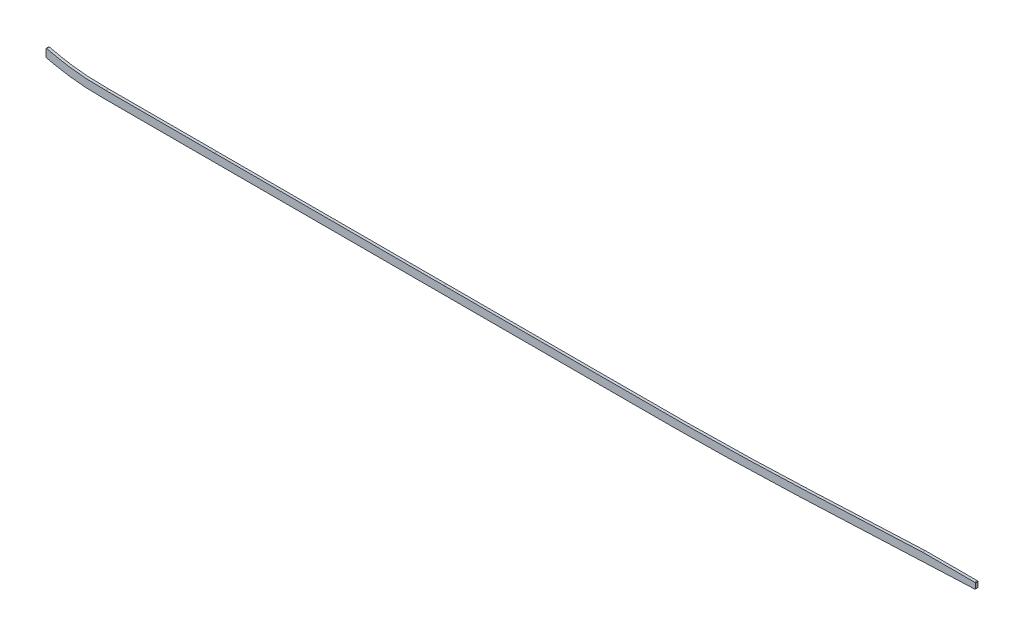
SolidWorks part; units mm, degrees
ref_plane "Front Plane" through (0, 0, 0) normal (0, 0, 1) x (1, 0, 0)
ref_plane "Top Plane" through (0, 0, 0) normal (0, 1, 0) x (1, 0, 0)
ref_plane "Right Plane" through (0, 0, 0) normal (1, 0, 0) x (0, 0, -1)
sketch "Sketch1" plane through (0, 0, 0) normal (0, 0, 1) x (1, 0, 0)
  line L0 (1046.2855, 53.4707) -> (499.61, 53.4707) construction
  line L1 (55, 0) -> (-55, 0) construction
  line L2 (1046.2855, -53.4707) -> (499.61, -53.4707)
  line L3 (1046.2855, -34.4207) -> (499.61, -34.4207)
  line L4 (99.06, -18.1493) -> (99.06, -37.7415)
  line L5 (2669.54, 9.5231) -> (2669.54, -9.569)
  spline S0 degree 5 poles (2699.7923, 7.5245) (2639.6368, 11.6572) (2579.4813, 15.4358) (2518.4981, 19.1485) (2436.3555, 23.2524) (2354.213, 26.6315) (2332.5703, 27.481) (2156.2686, 34.3778) (1979.9669, 41.6286) (1824.1143, 52.7713) (1636.9286, 53.5796) (1449.7429, 53.454) (1418.0067, 53.4707) (1324.8993, 53.4707) (1231.7919, 53.4707) (1170.4413, 53.4707) (1108.7841, 53.4707) (1047.1269, 53.4707) (1046.8464, 53.4707) (1046.5659, 53.4707) (1046.2855, 53.4707) knots 100.654805 100.654805 100.654805 100.654805 100.654805 100.654805 130.927897 130.927897 130.927897 141.337055 141.337055 141.337055 218.101815 218.101815 218.101815 233.772059 233.772059 233.772059 264.077723 264.077723 264.077723 264.216209 264.216209 264.216209 264.216209 264.216209 264.216209 weights 1 1 1 1 1 1 1 1 1 1 1 1 1 1 1 1 1 1 1 1 1 construction
  spline S1 degree 5 poles (499.61, 53.4707) (492.1368, 53.4707) (484.7543, 53.4707) (477.443, 53.4707) (448.5166, 53.4707) (419.5901, 53.4707) (398.3681, 53.4707) (355.6475, 53.4707) (312.927, 53.4707) (289.2351, 53.4703) (265.365, 53.4707) (241.4948, 53.4707) (241.4716, 53.4707) (241.4484, 53.4707) (241.4251, 53.4707) knots 19.90683 19.90683 19.90683 19.90683 19.90683 19.90683 23.637897 23.637897 23.637897 34.276546 34.276546 34.276546 46.401341 46.401341 46.401341 46.413154 46.413154 46.413154 46.413154 46.413154 46.413154 weights 1 1 1 1 1 1 1 1 1 1 1 1 1 1 1 construction
  spline S2 degree 5 poles (241.4251, 53.4707) (224.2869, 53.4707) (207.1495, 53.4673) (190.2039, 52.6866) (151.6561, 49.0319) (113.1083, 41.5037) (91.9499, 36.3426) (71.313, 30.9696) (50.6762, 24.7565) knots 0 0 0 0 0 0 8.713816 8.713816 8.713816 19.90683 19.90683 19.90683 19.90683 19.90683 19.90683 weights 1 1 1 1 1 1 1 1 1 construction
  spline S3 degree 5 poles (241.4251, -53.4707) (224.2869, -53.4707) (207.1495, -53.4673) (190.2039, -52.6866) (151.6561, -49.0319) (113.1083, -41.5037) (91.9499, -36.3426) (71.313, -30.9696) (50.6762, -24.7565) knots 0 0 0 0 0 0 8.713816 8.713816 8.713816 19.90683 19.90683 19.90683 19.90683 19.90683 19.90683 weights 1 1 1 1 1 1 1 1 1
  spline S4 degree 5 poles (499.61, -53.4707) (492.1368, -53.4707) (484.7543, -53.4707) (477.443, -53.4707) (448.5166, -53.4707) (419.5901, -53.4707) (398.3681, -53.4707) (355.6475, -53.4707) (312.927, -53.4707) (289.2351, -53.4703) (265.365, -53.4707) (241.4948, -53.4707) (241.4716, -53.4707) (241.4484, -53.4707) (241.4251, -53.4707) knots 19.90683 19.90683 19.90683 19.90683 19.90683 19.90683 23.637897 23.637897 23.637897 34.276546 34.276546 34.276546 46.401341 46.401341 46.401341 46.413154 46.413154 46.413154 46.413154 46.413154 46.413154 weights 1 1 1 1 1 1 1 1 1 1 1 1 1 1 1
  spline S5 degree 5 poles (2699.7923, -7.5245) (2639.6368, -11.6572) (2579.4813, -15.4358) (2518.4981, -19.1485) (2436.3555, -23.2524) (2354.213, -26.6315) (2332.5703, -27.481) (2156.2686, -34.3778) (1979.9669, -41.6286) (1824.1143, -52.7713) (1636.9286, -53.5796) (1449.7429, -53.454) (1418.0067, -53.4707) (1324.8993, -53.4707) (1231.7919, -53.4707) (1170.4413, -53.4707) (1108.7841, -53.4707) (1047.1269, -53.4707) (1046.8464, -53.4707) (1046.5659, -53.4707) (1046.2855, -53.4707) knots 100.654805 100.654805 100.654805 100.654805 100.654805 100.654805 130.927897 130.927897 130.927897 141.337055 141.337055 141.337055 218.101815 218.101815 218.101815 233.772059 233.772059 233.772059 264.077723 264.077723 264.077723 264.216209 264.216209 264.216209 264.216209 264.216209 264.216209 weights 1 1 1 1 1 1 1 1 1 1 1 1 1 1 1 1 1 1 1 1 1
  spline S6 degree 1 poles (2698.4867, 11.4807) (1046.2855, -34.4207) knots 0 0 1 1 construction
  spline S7 degree 1 poles (499.61, -34.4207) (241.4252, -34.4207) knots 0 0 1 1 construction
  spline S8 degree 1 poles (241.4252, -34.4207) (56.168, -6.5153) knots 0 0 1 1 construction
  spline S9 degree 3 poles (2698.4867, 11.4807) (2691.2474, 10.9833) (2679.1952, 10.1655) (2662.2765, 9.0388) (2635.6663, 7.2925) (2596.8577, 4.8261) (2545.7297, 1.7583) (2494.4053, -1.0986) (2451.533, -3.2666) (2417.1983, -4.8671) (2391.4571, -6.0036) (2365.6347, -7.0869) (2339.5463, -8.1377) (2313.4661, -9.1651) (2287.6124, -10.1795) (2261.7633, -11.201) (2227.2853, -12.5838) (2184.1756, -14.3661) (2132.4291, -16.6074) (2063.4255, -19.7089) (1977.1749, -23.7005) (1873.7325, -28.1494) (1770.3746, -31.6575) (1667.0857, -33.7931) (1581.0111, -34.3832) (1512.074, -34.4278) (1443.0615, -34.4095) (1356.8009, -34.4244) (1218.7946, -34.4185) (1115.289, -34.4207) (1046.2855, -34.4207) knots 100.654805 100.654805 100.654805 100.654805 102.842388 104.300777 105.766098 110.877392 115.988686 121.09998 126.211274 128.766921 131.322568 133.878215 136.433862 138.989509 141.545156 144.100803 146.656449 151.767743 156.879037 161.990331 172.212919 182.435507 192.658094 202.880682 213.10327 218.214564 223.325858 233.548445 243.771033 264.216209 264.216209 264.216209 264.216209
  spline S10 degree 3 poles (499.61, -34.4207) (488.6147, -34.4207) (472.2364, -34.4207) (449.9402, -34.4207) (427.7713, -34.4207) (405.8747, -34.4207) (384.5849, -34.4207) (368.9002, -34.4207) (353.3766, -34.4207) (332.6085, -34.4207) (306.2878, -34.4206) (274.0235, -34.4205) (252.271, -34.4207) (241.4252, -34.4207) knots 19.90683 19.90683 19.90683 19.90683 23.22012 24.876765 26.533411 29.846701 31.503346 33.159992 34.816637 36.473282 39.786573 43.099863 46.413154 46.413154 46.413154 46.413154
  spline S11 degree 3 poles (241.4252, -34.4207) (239.3949, -34.4207) (235.3223, -34.4205) (227.2744, -34.3987) (217.3194, -34.2975) (205.5307, -33.9764) (189.9633, -33.2126) (170.697, -31.5435) (147.5333, -28.3144) (125.4828, -24.2021) (107.4399, -20.1965) (92.2061, -16.4882) (75.9505, -12.2555) (63.6202, -8.7589) (56.168, -6.5153) knots 0 0 0 0 0.622088 1.244177 2.488354 3.732531 4.976707 7.465061 9.953415 12.441768 14.558235 15.802412 17.418476 19.90683 19.90683 19.90683 19.90683
  point P2 (0, 0)
  dimension "D1" = 50.6762
  dimension "D3" = 99.06
  dimension "D4" = 2669.54
  dimension "D2" = 19.05
extrude "Boss-Extrude1" add sketch "Sketch1" along normal mid plane 6.35 contours S10 S11 L4 S3 S4 L2 S5 L5 S9 L3 region at (1384.0143, -36.0059, 0)
sketch "Sketch2" plane through (0, 0, 3.175) normal (0, 0, 1) x (1, 0, 0)
  line L0 (2185.533, -14.3257) -> (2311.4, -14.3257)
  line L1 (2311.4, -14.3257) -> (2311.4, -9.2457)
  line L2 (2311.4, -14.3257) -> (2311.4, -28.3104)
  line L3 (2669.54, 9.5231) -> (2669.54, -9.569) construction
  line L4 (2669.54, 9.5231) -> (2669.54, -9.569)
  spline S0 degree 3 poles (689.0175, 232.3189) (4033.8285, 148.9311) (3356.6623, 54.6077) (2635.6663, 7.2925) (2596.8577, 4.8261) (2545.7297, 1.7583) (2494.4053, -1.0986) (2451.533, -3.2666) (2417.1983, -4.8671) (2391.4571, -6.0036) (2365.6347, -7.0869) (2339.5463, -8.1377) (2313.4661, -9.1651) (2287.6124, -10.1795) (2261.7633, -11.201) (2227.2853, -12.5838) (2184.1756, -14.3661) (2132.4291, -16.6074) (2063.4255, -19.7089) (1977.1749, -23.7005) (1873.7325, -28.1494) (1770.3746, -31.6575) (1667.0857, -33.7931) (1581.0111, -34.3832) (1512.074, -34.4278) (1443.0615, -34.4095) (1356.8009, -34.4244) (551.9641, -34.3896) (-218.4198, -34.7282) (-953.6342, -29.9632) knots -106.828462 -106.828462 -106.828462 -106.828462 104.300777 105.766098 110.877392 115.988686 121.09998 126.211274 128.766921 131.322568 133.878215 136.433862 138.989509 141.545156 144.100803 146.656449 151.767743 156.879037 161.990331 172.212919 182.435507 192.658094 202.880682 213.10327 218.214564 223.325858 233.548445 243.771033 461.793666 461.793666 461.793666 461.793666 only from (2669.54, 9.5231) to (1046.2855, -34.4207) construction
  spline S1 degree 3 poles (2669.54, 9.5231) (2667.1265, 9.3624) (2659.8616, 8.8803) (2635.6663, 7.2925) (2596.8577, 4.8261) (2545.7297, 1.7583) (2494.4053, -1.0986) (2451.533, -3.2666) (2417.1983, -4.8671) (2391.4571, -6.0036) (2365.6347, -7.0869) (2339.5463, -8.1377) (2313.4661, -9.1651) (2287.6124, -10.1795) (2261.7633, -11.201) (2227.2853, -12.5838) (2184.1756, -14.3661) (2132.4291, -16.6074) (2063.4255, -19.7089) (1977.1749, -23.7005) (1873.7325, -28.1494) (1770.3746, -31.6575) (1667.0857, -33.7931) (1581.0111, -34.3832) (1512.074, -34.4278) (1443.0615, -34.4095) (1356.8009, -34.4244) (1218.7946, -34.4185) (1115.289, -34.4207) (1046.2855, -34.4207) knots 103.571583 103.571583 103.571583 103.571583 104.300777 105.766098 110.877392 115.988686 121.09998 126.211274 128.766921 131.322568 133.878215 136.433862 138.989509 141.545156 144.100803 146.656449 151.767743 156.879037 161.990331 172.212919 182.435507 192.658094 202.880682 213.10327 218.214564 223.325858 233.548445 243.771033 264.216209 264.216209 264.216209 264.216209
  spline S2 degree 5 poles (4524.4896, 699.6349) (3179.77, -69.42) (3083.4624, 36.6115) (2859.542, 1.0131) (2606.8775, -16.2376) (2354.213, -26.6315) (2332.5703, -27.481) (2156.2686, -34.3778) (1979.9669, -41.6286) (1824.1143, -52.7713) (1636.9286, -53.5796) (1449.7429, -53.454) (1418.0067, -53.4707) (1324.8993, -53.4707) (1231.7919, -53.4707) (1170.4413, -53.4707) (970.3038, -53.4707) (770.1663, -53.4707) (702.0423, -53.4707) (-16.6162, -53.4711) (3039.7057, -53.1927) knots 16.201417 16.201417 16.201417 16.201417 16.201417 16.201417 130.927897 130.927897 130.927897 141.337055 141.337055 141.337055 218.101815 218.101815 218.101815 233.772059 233.772059 233.772059 264.077723 264.077723 264.077723 332.592886 332.592886 332.592886 332.592886 332.592886 332.592886 weights 1 1 1 1 1 1 1 1 1 1 1 1 1 1 1 1 1 1 1 1 1 only from (2669.54, -9.569) to (1046.2855, -53.4707) construction
  spline S3 degree 5 poles (2669.54, -9.569) (2615.3936, -13.1707) (2561.0807, -16.5361) (2506.2052, -19.7586) (2430.2091, -23.5052) (2354.213, -26.6315) (2332.5703, -27.481) (2156.2686, -34.3778) (1979.9669, -41.6286) (1824.1143, -52.7713) (1636.9286, -53.5796) (1449.7429, -53.454) (1418.0067, -53.4707) (1324.8993, -53.4707) (1231.7919, -53.4707) (1170.4413, -53.4707) (1108.7841, -53.4707) (1047.1269, -53.4707) (1046.8464, -53.4707) (1046.5659, -53.4707) (1046.2855, -53.4707) knots 103.698914 103.698914 103.698914 103.698914 103.698914 103.698914 130.927897 130.927897 130.927897 141.337055 141.337055 141.337055 218.101815 218.101815 218.101815 233.772059 233.772059 233.772059 264.077723 264.077723 264.077723 264.216209 264.216209 264.216209 264.216209 264.216209 264.216209 weights 1 1 1 1 1 1 1 1 1 1 1 1 1 1 1 1 1 1 1 1 1
  point P2 (0, 0)
  spline M7 degree 5 poles (1046.2855, -53.4707) (1046.5659, -53.4707) (1046.8464, -53.4707) (1047.1269, -53.4707) (1108.7841, -53.4707) (1170.4413, -53.4707) (1231.7919, -53.4707) (1324.8993, -53.4707) (1418.0067, -53.4707) (1449.7429, -53.454) (1636.9286, -53.5796) (1824.1143, -52.7713) (1979.9669, -41.6286) (2156.2686, -34.3778) (2332.5703, -27.481) (2354.213, -26.6315) (2436.3555, -23.2524) (2518.4981, -19.1485) (2579.4813, -15.4358) (2639.6368, -11.6572) (2699.7923, -7.5245) knots 100.654805 100.654805 100.654805 100.654805 100.654805 100.654805 100.79329 100.79329 100.79329 131.098954 131.098954 131.098954 146.769198 146.769198 146.769198 223.533959 223.533959 223.533959 233.943117 233.943117 233.943117 264.216209 264.216209 264.216209 264.216209 264.216209 264.216209 weights 1 1 1 1 1 1 1 1 1 1 1 1 1 1 1 1 1 1 1 1 1 only from (1046.2855, -53.4707) to (2669.54, -9.569)
  line M8 (2669.54, -9.569) -> (2669.54, 9.5231)
  spline M9 degree 3 poles (2698.4867, 11.4807) (2691.2474, 10.9833) (2679.1952, 10.1655) (2662.2765, 9.0388) (2635.6663, 7.2925) (2596.8577, 4.8261) (2545.7297, 1.7583) (2494.4053, -1.0986) (2451.533, -3.2666) (2417.1983, -4.8671) (2391.4571, -6.0036) (2365.6347, -7.0869) (2339.5463, -8.1377) (2313.4661, -9.1651) (2287.6124, -10.1795) (2261.7633, -11.201) (2227.2853, -12.5838) (2184.1756, -14.3661) (2132.4291, -16.6074) (2063.4255, -19.7089) (1977.1749, -23.7005) (1873.7325, -28.1494) (1770.3746, -31.6575) (1667.0857, -33.7931) (1581.0111, -34.3832) (1512.074, -34.4278) (1443.0615, -34.4095) (1356.8009, -34.4244) (1218.7946, -34.4185) (1115.289, -34.4207) (1046.2855, -34.4207) knots 100.654805 100.654805 100.654805 100.654805 102.842388 104.300777 105.766098 110.877392 115.988686 121.09998 126.211274 128.766921 131.322568 133.878215 136.433862 138.989509 141.545156 144.100803 146.656449 151.767743 156.879037 161.990331 172.212919 182.435507 192.658094 202.880682 213.10327 218.214564 223.325858 233.548445 243.771033 264.216209 264.216209 264.216209 264.216209 only from (2669.54, 9.5231) to (1046.2855, -34.4207)
  dimension "D1" = 2311.4
  dimension "D2" = 5.08
extrude "Cut-Extrude1" cut sketch "Sketch2" against normal through all contours L0 L1 M9 | L1 L2 M7 M8 M9 region at (2269.1304, -12.6229, 3.175) region at (2490.5174, -10.3074, 3.175)
fillet "Fillet1" radius 1.27 4 edges at (99.06, -37.7415, 0) (99.06, -18.1493, 0)
